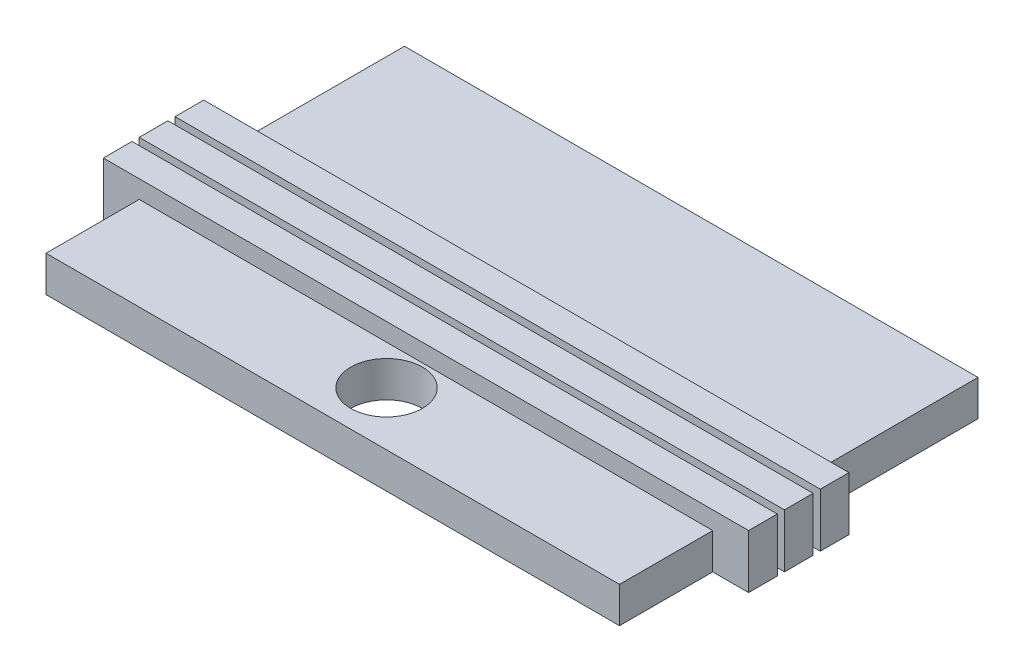
SolidWorks part; units mm, degrees
ref_plane "Front Plane" through (0, 0, 0) normal (0, 0, 1) x (1, 0, 0)
ref_plane "Top Plane" through (0, 0, 0) normal (0, 1, 0) x (1, 0, 0)
ref_plane "Right Plane" through (0, 0, 0) normal (1, 0, 0) x (0, 0, -1)
sketch "Sketch1" plane through (0, 0, 0) normal (0, 1, 0) x (1, 0, 0)
  line L5 (-40, 25) -> (40, 25)
  line L6 (-40, 25) -> (-40, -25)
  line L11 (-40, -25) -> (40, -25)
  line L12 (40, 25) -> (40, -25)
  line L17 (-40, 25) -> (40, -25) construction
  line L18 (-40, -25) -> (40, 25) construction
  line L19 (-45, 2) -> (45, 2)
  line L20 (-45, 2) -> (-45, -2)
  line L21 (-45, -2) -> (45, -2)
  line L22 (45, 2) -> (45, -2)
  line L23 (-45, 2) -> (45, -2) construction
  line L24 (-45, -2) -> (45, 2) construction
  line L25 (-45, -3) -> (45, -3)
  line L26 (-45, -3) -> (-45, -7)
  line L27 (-45, -7) -> (45, -7)
  line L28 (45, -3) -> (45, -7)
  line L29 (-45, -3) -> (45, -7) construction
  line L30 (-45, -7) -> (45, -3) construction
  line L31 (-45, -8) -> (45, -8)
  line L32 (-45, -8) -> (-45, -12)
  line L33 (-45, -12) -> (45, -12)
  line L34 (45, -8) -> (45, -12)
  line L35 (-45, -8) -> (45, -12) construction
  line L36 (-45, -12) -> (45, -8) construction
  circle A1 centre (0, -17.5) radius 5
  point P0 (0, 0)
  point P6 (0, 0)
  point P11 (0, -5)
  point P22 (0, -10)
  dimension "D6" = 17.5
  dimension "D5" = 10
  dimension "D1" = 80
  dimension "D2" = 90
  dimension "D4" = 50
  dimension "D7" = 4
  dimension "D8" = 5
  dimension "D9" = 5
extrude "Boss-Extrude1" add sketch "Sketch1" along normal blind 5 contours L6 L11 L12 L5
extrude "Boss-Extrude2" add sketch "Sketch1<3>" along normal blind 7.5 contours L20 L21 L22 L19 | L26 L27 L28 L25 | L32 L33 L34 L31
sketch "Sketch1<3>" plane through (0, 0, 0) normal (0, 1, 0) x (1, 0, 0) same geometry as "Sketch1"
extrude "Cut-Extrude1" cut sketch "Sketch1<4>" along normal up to surface (5 mm away) contours A1 up to face at (0, 5, 18.5)
sketch "Sketch1<4>" plane through (0, 0, 0) normal (0, 1, 0) x (1, 0, 0) same geometry as "Sketch1"
